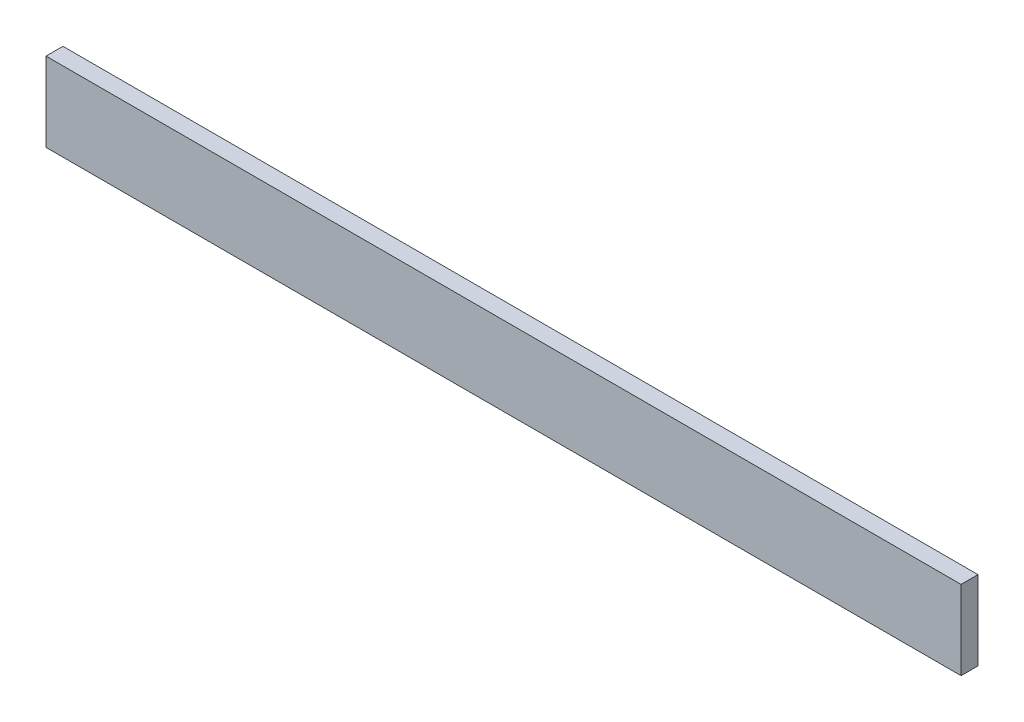
SolidWorks part; units mm, degrees
material "Cedar"
ref_plane "Front Plane" through (0, 0, 0) normal (0, 0, 1) x (1, 0, 0)
ref_plane "Top Plane" through (0, 0, 0) normal (0, 1, 0) x (1, 0, 0)
ref_plane "Right Plane" through (0, 0, 0) normal (1, 0, 0) x (0, 0, -1)
sketch "Sketch1" plane through (0, 0, 0) normal (1, 0, 0) x (0, 0, -1)
  line L1 (-9.525, -44.45) -> (9.525, -44.45)
  line L2 (-9.525, -44.45) -> (-9.525, 44.45)
  line L3 (-9.525, 44.45) -> (9.525, 44.45)
  line L4 (9.525, -44.45) -> (9.525, 44.45)
  line L5 (-9.525, -44.45) -> (9.525, 44.45) construction
  line L6 (-9.525, 44.45) -> (9.525, -44.45) construction
  point P0 (0, 0)
  dimension "D1" = 88.9
  dimension "D2" = 19.05
extrude "Boss-Extrude1" add sketch "Sketch1" along normal blind 514.35 and the other way blind 514.35
